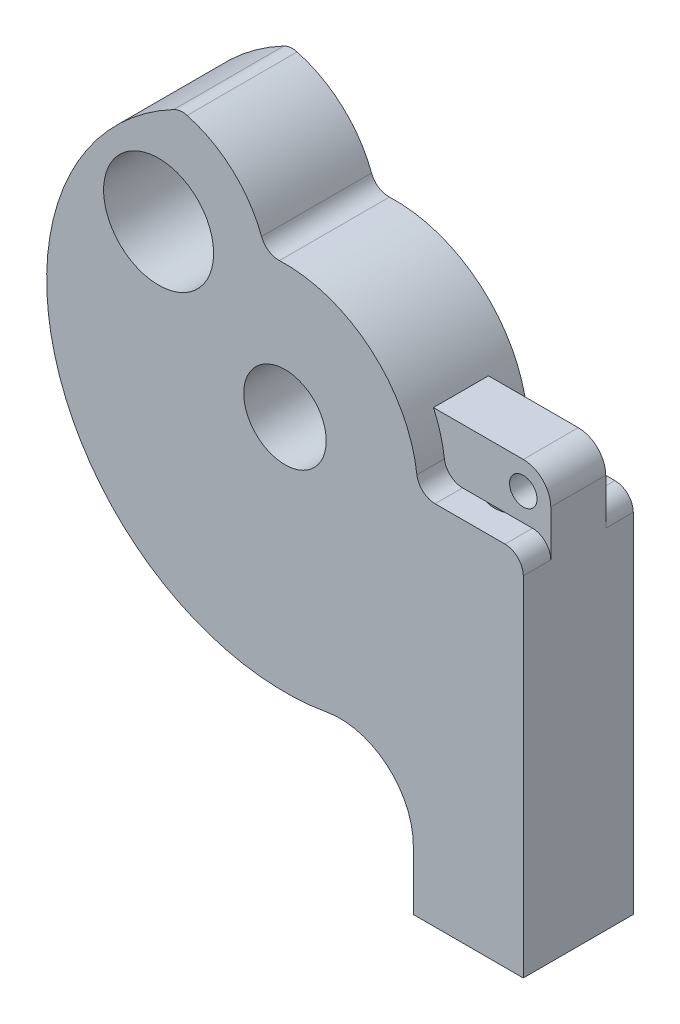
SolidWorks part; units mm, degrees
ref_plane "Front Plane" through (0, 0, 0) normal (0, 0, 1) x (1, 0, 0)
ref_plane "Top Plane" through (0, 0, 0) normal (0, 1, 0) x (1, 0, 0)
ref_plane "Right Plane" through (0, 0, 0) normal (1, 0, 0) x (0, 0, -1)
sketch "Sketch2" plane through (0, 0, 0) normal (0, 0, 1) x (1, 0, 0)
  line L0 (13, 0) -> (13, -20)
  line L1 (13, -20) -> (7, -20)
  line L2 (7, -20) -> (7, -10.9545)
  line L3 (10, 0) -> (10, -20) construction
  arc A0 (13, 0) -> (7, -10.9545) centre (0, 0) ccw
  circle A1 centre (0, 0) radius 10 construction
  dimension "Diameter" = 20
  dimension "Rod Holer Thickness" = 6
  dimension "Rod Holder Length" = 20
extrude "Boss-Extrude1" add sketch "Sketch2" along normal mid plane 6
hole_wizard "M4 Clearance Hole1" positions "Sketch3" profile "Sketch4" hole size "M4" standard "ANSI Metric" end condition up to next
sketch "Sketch3" plane through (0, 0, 3) normal (0, 0, 1) x (1, 0, 0)
  point P2 (0, 0)
sketch "Sketch4" plane through (0, 0, 3) normal (1, 0, 0) x (0, -1, 0)
  line L0 (0, 0) -> (0, 6)
  line L1 (0, 6) -> (2.25, 6)
  line L2 (2.25, 6) -> (2.25, 0)
  line L5 (2.25, 0) -> (0, 0)
  line L11 (0, -6.35) -> (0, 107.95) construction
  dimension "Thru Hole Dia." = 4.5
  dimension "Thru Hole Depth" = 6
sketch "Sketch5" plane through (0, -20, 0) normal (0, -1, 0) x (1, 0, 0)
  line L0 (13, 3) -> (7, -3) construction
  circle A0 centre (10, 0) radius 1.59
  dimension "Rod Hole Diameter" = 3.18
extrude "Cut-Extrude1" cut sketch "Sketch5" against normal blind 20
ref_axis "Axis1" through (10, 0, 0) along (0, -1, 0)
sketch "Sketch8" plane through (0, 0, 3) normal (0, 0, 1) x (1, 0, 0)
  line L0 (0, 0) -> (-21.8723, 0) construction
  line L1 (0, 0) -> (-6.8944, 5.7851) construction
  circle A0 centre (-6.8944, 5.7851) radius 3
  dimension "D2" = 6
  dimension "D1" = 40
  dimension "D3" = 9
extrude "Cut-Extrude3" cut sketch "Sketch8" against normal through all
sketch "Sketch9" plane through (0, 0, 3) normal (0, 0, 1) x (1, 0, 0)
  line L1 (13, 0) -> (7.25, 0)
  line L2 (13, 0) -> (13, 10.075) construction
  arc A0 (13, 0) -> (7, -10.9545) centre (0, 0) ccw construction
  arc A1 (7.25, 0) -> (-1.057, 7.1725) centre (0, 0) ccw
  circle A2 centre (0, 0) radius 2.25 construction
  arc A4 (-1.057, 7.1725) -> (-5.7272, 11.6705) centre (-6.8944, 5.7851) ccw
  circle A5 centre (-6.8944, 5.7851) radius 3 construction
  arc A6 (13, 0) -> (-5.7272, 11.6705) centre (0, 0) ccw
  dimension "D1" = 5
  dimension "D2" = 3
extrude "Cut-Extrude4" cut sketch "Sketch9" against normal through all
sketch "Sketch6" plane through (0, 0, 0) normal (0, 0, 1) x (1, 0, 0)
  line L4 (13, 1.5) -> (13, 0)
  line L6 (11.5, 3) -> (6.6002, 3)
  line L8 (7.25, 0) -> (13, 0) construction
  line L9 (7.25, 0) -> (13, 0)
  arc A2 (13, 1.5) -> (11.5, 3) centre (11.5, 1.5) ccw
  arc A3 (7.25, 0) -> (-1.057, 7.1725) centre (0, 0) ccw construction
  arc A4 (7.25, 0) -> (6.6002, 3) centre (0, 0) ccw
  dimension "Spring Attchment Diameter" = 1.5
extrude "Boss-Extrude2" add sketch "Sketch6" along normal mid plane 3
fillet "Fillet1" radius 1 6 edges at (-5.7272, 11.6705, 0) (7.25, 0, 2.25) (7.25, 0, -2.25) (-1.057, 7.1725, 0) (13, 0, -2.25) (13, 0, 2.25)
sketch "Sketch7" plane through (0, 0, 1.5) normal (0, 0, 1) x (1, 0, 0)
  circle A0 centre (11.5, 1.5) radius 0.75
  arc A1 (13, 1.5) -> (11.5, 3) centre (11.5, 1.5) ccw construction
  dimension "Spring Hole Diam" = 1.5
extrude "Cut-Extrude2" cut sketch "Sketch7" against normal through all both and the other way through all
fillet "Fillet2" radius 4 1 edges at (7, -10.9545, 0)
